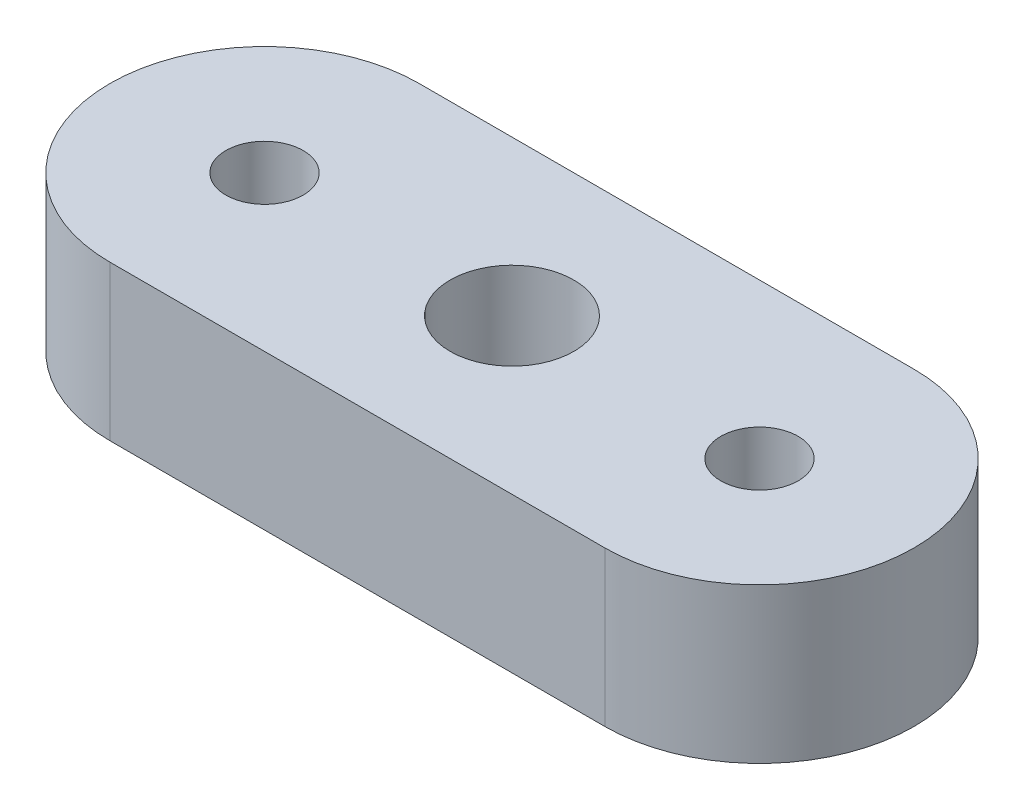
SolidWorks part; units mm, degrees
ref_plane "Plano frontal" through (0, 0, 0) normal (0, 0, 1) x (1, 0, 0)
ref_plane "Plano superior" through (0, 0, 0) normal (0, 1, 0) x (1, 0, 0)
ref_plane "Plano direito" through (0, 0, 0) normal (1, 0, 0) x (0, 0, -1)
sketch "Esboço1" plane through (0, 0, 0) normal (0, 1, 0) x (1, 0, 0)
  circle A0 centre (0, 0) radius 4
  circle A1 centre (16, 0) radius 2.5
  circle A2 centre (-16, 0) radius 2.5
sketch "Esboço2" plane through (0, 0, 0) normal (0, 1, 0) x (1, 0, 0)
  line L0 (16, 10) -> (-16, 10)
  line L1 (-16, -10) -> (16, -10)
  arc A0 (16, -10) -> (16, 10) centre (16, 0) ccw
  arc A1 (-16, 10) -> (-16, -10) centre (-16, 0) ccw
  point P3 (0, 0)
  point P7 (0, 0)
  point P8 (0, 0)
  point P10 (0, 0)
extrude "Ressalto-extrusão1" add sketch "Esboço2" along normal blind 5 and the other way blind 5
extrude "Corte-extrusão1" cut sketch "Esboço1" against normal blind 5 and the other way blind 5
